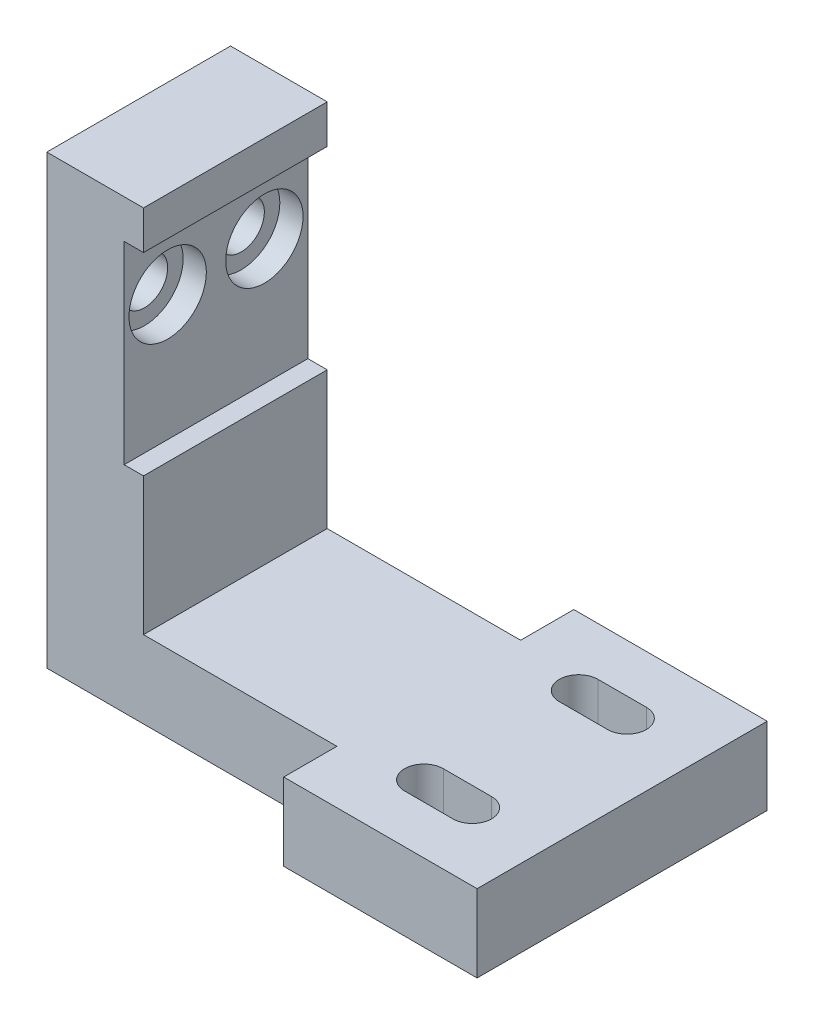
SolidWorks part; units mm, degrees
material "6061-T6 (SS)"
ref_plane "Front Plane" through (0, 0, 0) normal (0, 0, 1) x (1, 0, 0)
ref_plane "Top Plane" through (0, 0, 0) normal (0, 1, 0) x (1, 0, 0)
ref_plane "Right Plane" through (0, 0, 0) normal (1, 0, 0) x (0, 0, -1)
sketch "Sketch1" plane through (0, 0, 0) normal (0, 0, 1) x (1, 0, 0)
  line L0 (-15.4886, 8) -> (-17.5374, 8) construction
  line L9 (-17.5374, 3) -> (-17.5374, 13)
  line L10 (-21.5374, 0) -> (-21.5374, 15)
  line L11 (-21.5374, 15) -> (-16.5374, 15)
  line L12 (-16.5374, 15) -> (-16.5374, 13)
  line L17 (-12.4274, -4.11) -> (3.4626, -4.11)
  line L18 (3.4626, -4.11) -> (3.4626, -8.11)
  line L19 (3.4626, -8.11) -> (-13.4274, -8.11)
  line L20 (-17.5374, 13) -> (-16.5374, 13)
  line L21 (-17.5374, 3) -> (-16.5374, 3)
  line L22 (-16.5374, 3) -> (-16.5374, 0)
  line L23 (-21.5374, 0) -> (-21.5374, -8.11)
  line L24 (-21.5374, -8.11) -> (-13.4274, -8.11)
  line L25 (-16.5374, 0) -> (-16.5374, -4.11)
  line L26 (-16.5374, -4.11) -> (-12.4274, -4.11)
  line L29 (-12.4274, -4.11) -> (-10.0144, -4.11) construction
  point P15 (-17.5374, 8)
  point P21 (-12.4274, 0)
  dimension "D4" = 3
  dimension "D2" = 5
  dimension "D5" = 25
  dimension "D6" = 10
  dimension "D7" = 2
  dimension "D8" = 1
  dimension "D10" = 4
extrude "Boss-Extrude1" add sketch "Sketch1" along normal mid plane 9.5
sketch "Sketch2" plane through (-17.5374, 0, 0) normal (1, 0, 0) x (0, 0, -1)
  line L0 (-4.75, 8) -> (4.75, 8) construction
  line L1 (-4.75, 3) -> (-4.75, 13) construction
  line L2 (4.75, 3) -> (4.75, 13) construction
  line L3 (-4.75, 9.5) -> (4.75, 9.5) construction
  line L4 (0, 9.5) -> (0, 8) construction
  point P8 (-2.5, 9.5)
  point P11 (2.5, 9.5)
  dimension "D2" = 2.5
  dimension "D1" = 1.5
hole_wizard "M2 Clearance Hole1" positions "3DSketch1" profile "Sketch3" hole size "M2" standard "ANSI Metric" end condition through all
sketch3d "3DSketch1"
  point P0 (-17.5374, 9.5, 2.5)
  point P3 (-17.5374, 9.5, -2.5)
sketch "Sketch3" plane through (-17.5374, 9.5, 2.5) normal (0, 1, 0) x (0, 0, -1)
  line L0 (0, 0) -> (0, 4)
  line L1 (0, 4) -> (1.2, 4)
  line L2 (1.2, 4) -> (1.2, 0)
  line L5 (1.2, 0) -> (0, 0)
  line L11 (0, -6.35) -> (0, 107.95) construction
  dimension "Thru Hole Dia." = 2.4
  dimension "Thru Hole Depth" = 4
sketch "Sketch4" plane through (-17.5374, 0, 0) normal (1, 0, 0) x (0, 0, -1)
  circle A0 centre (-2.5, 9.5) radius 2
  circle A1 centre (2.5, 9.5) radius 2
  dimension "D1" = 4
  dimension "D2" = 4
extrude "Cut-Extrude1" cut sketch "Sketch4" against normal blind 1.2
sketch "Sketch5" plane through (0, -8.11, 0) normal (0, -1, 0) x (1, 0, 0)
  line L0 (3.4626, -7.5) -> (3.4626, 7.5)
  line L1 (3.4626, 4.75) -> (3.4626, -4.75) construction
  line L2 (3.4626, 7.5) -> (-6.5374, 7.5)
  line L3 (-6.5374, 7.5) -> (-6.5374, -7.5)
  line L4 (-6.5374, -7.5) -> (3.4626, -7.5)
  point P3 (3.4626, 0)
  dimension "D1" = 10
  dimension "D2" = 15
extrude "Boss-Extrude2" add sketch "Sketch5" against normal blind 4
sketch "Sketch6" plane through (0, -4.11, 0) normal (0, 1, 0) x (1, 0, 0)
  line L0 (3.4626, 0) -> (-6.5374, 0) construction
  line L1 (3.4626, 7.5) -> (3.4626, -7.5) construction
  line L2 (-0.2874, -4) -> (-2.7874, -4) construction
  line L3 (-1.5374, -7.5) -> (-1.5374, 7.5) construction
  line L4 (3.4626, -7.5) -> (-6.5374, -7.5) construction
  line L5 (-6.5374, 7.5) -> (3.4626, 7.5) construction
  line L6 (-0.2874, -5) -> (-2.7874, -5)
  line L7 (-0.2874, -3) -> (-2.7874, -3)
  line L8 (-0.2874, 4) -> (-2.7874, 4) construction
  line L9 (-0.2874, 5) -> (-2.7874, 5)
  line L10 (-0.2874, 3) -> (-2.7874, 3)
  arc A0 (-0.2874, -5) -> (-0.2874, -3) centre (-0.2874, -4) ccw
  arc A1 (-2.7874, -3) -> (-2.7874, -5) centre (-2.7874, -4) ccw
  arc A2 (-0.2874, 5) -> (-0.2874, 3) centre (-0.2874, 4) cw
  arc A3 (-2.7874, 3) -> (-2.7874, 5) centre (-2.7874, 4) cw
  point P12 (-1.5374, -4)
  point P13 (-1.5374, 0)
  point P14 (-1.5374, 4)
  point P15 (-1.5374, -4)
  point P20 (0, 0)
  point P23 (-1.5374, 4)
  dimension "D3" = 1
  dimension "D1" = 4
  dimension "D2" = 2.5
extrude "Cut-Extrude2" cut sketch "Sketch6" against normal up to surface (4 mm away) up to face at (-7.7874, -8.11, 0)
